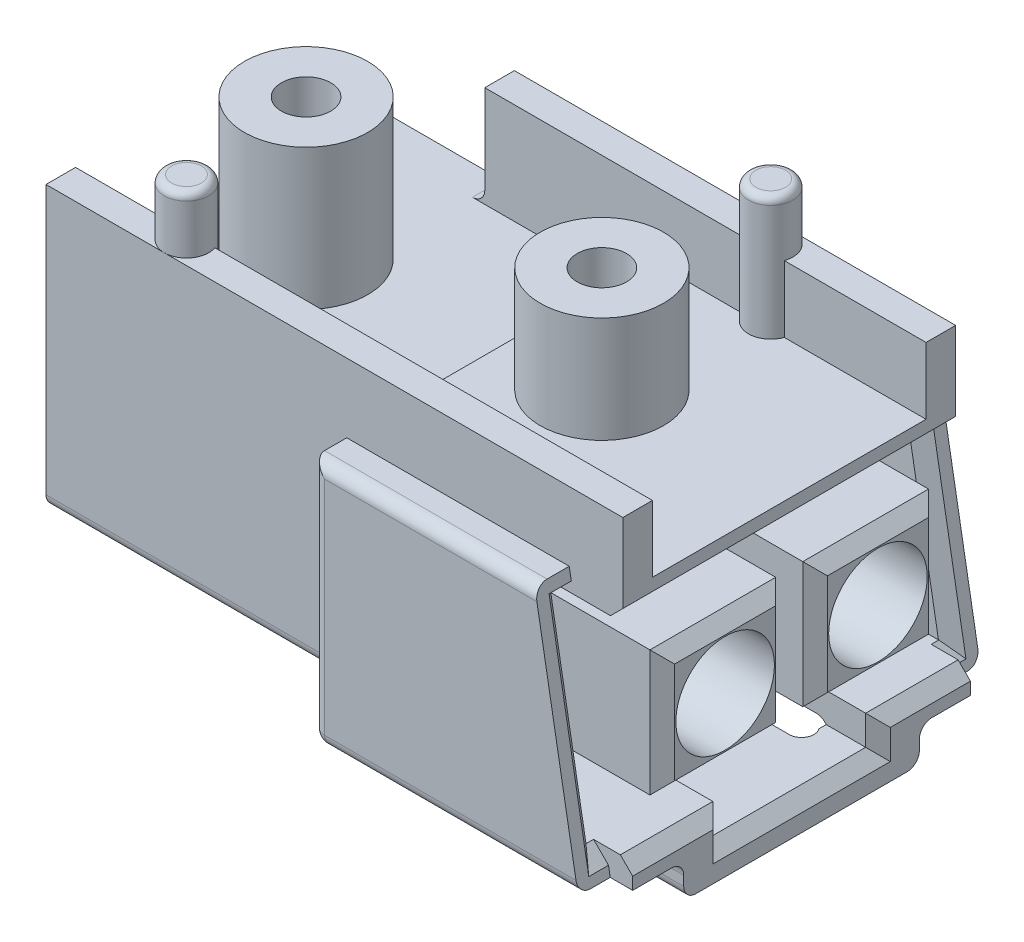
SolidWorks part; units mm, degrees
material "ABS PC"
ref_plane "Front Plane" through (0, 0, 0) normal (0, 0, 1) x (1, 0, 0)
ref_plane "Top Plane" through (0, 0, 0) normal (0, 1, 0) x (1, 0, 0)
ref_plane "Right Plane" through (0, 0, 0) normal (1, 0, 0) x (0, 0, -1)
sketch "Sketch1" plane through (0, 0, 0) normal (0, 0, 1) x (1, 0, 0)
  line L0 (7.1, 7.7) -> (7.1, 0)
  line L1 (-7.1, 7.3) -> (5.1, 7.3)
  line L2 (-7.1, 7.3) -> (-7.1, 0)
  line L3 (7.1, 0) -> (-7.1, 0)
  line L4 (16.3, 7.7) -> (7.1, 7.7)
  line L5 (5.1, 8.7) -> (16.3, 8.7)
  line L6 (16.3, 8.7) -> (16.3, 7.7)
  line L7 (5.1, 8.7) -> (5.1, 7.3)
  dimension "D1" = 14.2
  dimension "D2" = 7.3
  dimension "D3" = 7.7
  dimension "D4" = 1.4
  dimension "D5" = 12.2
  dimension "D6" = 11.2
extrude "Extrude1" add sketch "Sketch1" against normal blind 6.75
chamfer "Chamfer1" distance 0.5 angle 45 1 edges at (16.3, 7.7, -3.375)
sketch "Sketch2" plane through (7.1, 0, 0) normal (1, 0, 0) x (0, 0, -1)
  line L0 (5.65, 6.2) -> (0.55, 6.2)
  line L1 (5.65, 1.1) -> (5.65, 6.2)
  line L2 (0.55, 1.1) -> (5.65, 1.1)
  line L3 (0.55, 6.2) -> (0.55, 1.1)
  line L4 (0, 0) -> (0, 7.7) construction
  line L5 (6.75, 7.7) -> (0, 7.7) construction
  dimension "D1" = 5.1
  dimension "D2" = 5.1
  dimension "D3" = 0.55
  dimension "D4" = 1.5
extrude "Extrude2" add sketch "Sketch2" along normal blind 9.7
chamfer "Chamfer2" distance 0.5 angle 45 4 edges at (16.8, 1.1, -3.1) (16.8, 3.65, -5.65) (16.8, 6.2, -3.1) (16.8, 3.65, -0.55)
ref_plane "Plane1" through (0, 0, -3.1) normal (0, 0, 1) x (1, 0, 0)
sketch "Sketch4" plane through (0, 0, -3.1) normal (0, 0, 1) x (1, 0, 0)
  line L0 (-7.1, 3.65) -> (16.8, 3.65) construction
  line L1 (-7.1, 0.95) -> (2.35, 0.95)
  line L2 (2.35, 0.95) -> (3.4, 2)
  line L3 (5.8, 2.085) -> (6.05, 2.335)
  line L4 (3.4, 2) -> (5.8, 2)
  line L5 (6.05, 2.335) -> (7.95, 2.335)
  line L6 (7.95, 1.65) -> (7.95, 2.335)
  line L7 (7.95, 1.65) -> (16.8, 1.65)
  line L8 (5.8, 2) -> (5.8, 2.085)
  line L9 (16.8, 5.7) -> (16.8, 1.6) construction
  line L10 (-7.1, 0.95) -> (-7.1, 3.65)
  line L11 (16.8, 1.65) -> (16.8, 3.65)
  line L12 (16.8, 3.65) -> (-7.1, 3.65)
  dimension "D1" = 2
  dimension "D3" = 8.85
  dimension "D4" = 0.685
  dimension "D5" = 1.9
  dimension "D6" = 45
  dimension "D7" = 0.3536
  dimension "D8" = 0.085
  dimension "D9" = 2.4
  dimension "D10" = 45
  dimension "D11" = 1.4849
  dimension "D12" = 9.45
revolve "Cut-Revolve1" cut sketch "Sketch4" angle 360 about L0
sketch "Sketch5" plane through (5.1, 0, 0) normal (-1, 0, 0) x (0, 0, 1)
  line L0 (-3.1, -1.401) -> (-8.15, -1.401)
  line L1 (-8.15, 8.6) -> (-8.15, -1.401)
  line L2 (-6.75, 8.6) -> (-8.15, 8.6)
  line L3 (-3.1, 3.65) -> (-3.1, -1.401) construction
  line L4 (-3.1, -1.401) -> (-3.1, 0)
  line L5 (-6.75, 0) -> (0, 0) construction
  line L6 (-3.1, 0) -> (-6.75, 0)
  line L7 (-6.75, 0) -> (-6.75, 7.7) construction
  line L8 (-6.75, 8.6) -> (-6.75, 0)
  circle A0 centre (-3.1, 3.65) radius 1.315 construction
  dimension "D1" = 1.4
  dimension "D2" = 5.051
  dimension "D3" = 5.05
  dimension "D4" = 10.001
extrude "Extrude3" add sketch "Sketch5" against normal up to surface (2 mm away) up to face at (7.1, 3.85, -3.375)
sketch "Sketch6" plane through (0, 8.7, 0) normal (0, 1, 0) x (1, 0, 0)
  line L0 (14.1073, 0) -> (14.1073, 6.75) construction
  line L1 (16.3, 0) -> (5.1, 0) construction
  line L2 (16.3, 6.75) -> (5.1, 6.75) construction
  line L3 (16.3, 6.75) -> (16.3, 0) construction
  dimension "D1" = 2.1927
ref_plane "Plane2" through (15.1697, 2.6748, 0) normal (0.9848, 0.1736, 0) x (0, 0, -1)
sketch "Sketch8" plane through (7.1, 0, 0) normal (1, 0, 0) x (0, 0, -1)
  line L0 (8.15, -1.401) -> (3.1, -1.401) construction
  line L1 (8.15, 8.6) -> (8.15, -1.401) construction
  line L2 (6.75, 8.6) -> (8.15, 8.6) construction
  line L4 (8.15, -1.401) -> (3.1, -1.401)
  line L5 (8.15, 8.6) -> (8.15, -1.401)
  line L6 (6.75, 8.6) -> (8.15, 8.6)
  line L7 (6.75, 8.6) -> (6.75, 7.7)
  line L8 (3.1, -1.401) -> (3.1, -0.4)
  line L10 (3.1, -0.4) -> (7.15, -0.4)
  line L11 (3.1, 0) -> (0, 0) construction
  line L12 (6.75, 7.7) -> (7.15, 7.7)
  line L13 (7.15, 7.7) -> (7.15, -0.4)
  dimension "D1" = 0.4
  dimension "D2" = 0.4
extrude "Extrude5" add sketch "Sketch8" along normal up to surface (7.0249 mm away) up to plane "Plane2"
sketch "Sketch9" plane through (0, 0, -6.75) normal (0, 0, -1) x (-1, 0, 0)
  line L0 (-16.3, 8.7) -> (-16.3, 11.4)
  line L1 (-16.3, 11.4) -> (7.1, 11.4)
  line L2 (7.1, 11.4) -> (7.1, 7.3)
  line L3 (7.1, 7.3) -> (-5.1, 7.3)
  line L4 (-5.1, 7.3) -> (-5.1, 8.7)
  line L5 (-5.1, 8.7) -> (-16.3, 8.7)
  dimension "D1" = 2.7
extrude "Extrude6" add sketch "Sketch9" against normal blind 1.2
sketch "Sketch10" plane through (16.8, 0, 0) normal (1, 0, 0) x (0, 0, -1)
  line L0 (3.1, -0.4) -> (6.85, -0.4)
  line L1 (3.1, -0.4) -> (3.1, -1.6)
  line L2 (0, -1.6) -> (3.1, -1.6)
  line L3 (4.7801, -1.401) -> (6.85, -1.401)
  line L4 (4.7801, -1.401) -> (4.7801, -2.8)
  line L5 (0, -2.8) -> (4.7801, -2.8)
  line L6 (6.85, -0.4) -> (6.85, -1.401)
  line L7 (0, -1.6) -> (0, -2.8)
  line L8 (0, 0) -> (0, 7.7) construction
  line L9 (3.1, -1.401) -> (8.15, -1.401) construction
  point P10 (0, 0)
  dimension "D1" = 3.75
  dimension "D2" = 1.2
  dimension "D3" = 4.7801
  dimension "D4" = 1.2
extrude "Extrude7" add sketch "Sketch10" against normal blind 2
sketch "Sketch11" plane through (0, 0, 0) normal (0, 0, 1) x (1, 0, 0)
  line L0 (16.8, -1.6) -> (16.8, -2.8)
  line L1 (11.25, -1.6) -> (16.8, -1.6)
  line L2 (8.2, -1.6) -> (8.75, -1.6)
  line L3 (8.2, -1.6) -> (8.2, -2.8)
  line L4 (16.8, -2.8) -> (8.2, -2.8)
  arc A0 (11.25, -1.6) -> (8.75, -1.6) centre (10, -2.1766) ccw
  dimension "D3" = 1.3766
  dimension "D1" = 8.6
  dimension "D2" = 1.2
  dimension "D4" = 0.6234
  dimension "D5" = 1.8
  dimension "D6" = 0.55
extrude "Extrude8" add sketch "Sketch11" against normal blind 2
fillet "Fillet1" radius 0.5 12 edges at (10.4942, -1.401, -8.15) (5.1, -1.401, -5.625) (5.1, 3.5995, -8.15) (9.6124, 8.6, -8.15) (14.8, -2.8, -3.3901) (15.8, -2.8, -4.7801) (14.8, -2.1005, -4.7801) (14.8, -2.2, -2) (11.5, -2.8, -2) (8.2, -2.2, -2) (8.2, -2.8, -1) (-1, 0, -6.75)
fillet "Fillet2" radius 0.5 3 edges at (14.8, -1.401, -3.6901) (14.9464, -1.401, -4.6337) (16.05, -1.401, -4.7801)
chamfer "Chamfer4" distance 0.5 angle 45 6 edges at (15.7118, -0.4, -7) (14.2836, 7.7, -6.95) (14.9977, 3.65, -7.15) (16.8, -1.6, -1.55) (16.8, -1, -3.1) (16.8, -0.4, -4.975) first distance on face at (13.2039, -0.4, -5.7) first distance on face at (12.3945, 7.7, -4.6333) first distance on face at (11.0489, 3.65, -7.15) first distance on face at (14.2923, -1.6, -1.8396) first distance on face at (10.2799, -0.8622, -3.1)
sketch "Sketch13" plane through (0, 7.3, 0) normal (0, 1, 0) x (1, 0, 0)
  line L1 (5.1, 0) -> (-7.1, 0) construction
  line L2 (-7.1, 5.55) -> (-7.1, 0) construction
  line L3 (-0.8, 0) -> (-2.3, 0)
  line L4 (-4.3, 0) -> (-5.8, 0)
  arc A0 (-0.8, 0) -> (-5.8, 0) centre (-3.3, 0) ccw
  arc A1 (-2.3, 0) -> (-4.3, 0) centre (-3.3, 0) ccw
  dimension "D1" = 5
  dimension "D3" = 2
  dimension "D2" = 3.8
extrude "Extrude9" add sketch "Sketch13" along normal blind 5.7
sketch "Sketch14" plane through (0, 8.7, 0) normal (0, 1, 0) x (1, 0, 0)
  line L0 (16.3, 0) -> (5.1, 0) construction
  line L1 (5.1, 5.55) -> (5.1, 0) construction
  line L2 (11.2, 0) -> (9.7, 0)
  line L3 (7.7, 0) -> (6.2, 0)
  arc A0 (11.2, 0) -> (6.2, 0) centre (8.7, 0) ccw
  arc A1 (9.7, 0) -> (7.7, 0) centre (8.7, 0) ccw
  dimension "D2" = 5
  dimension "D3" = 2
  dimension "D1" = 3.6
extrude "Extrude10" add sketch "Sketch14" along normal blind 4.3
mirror "Mirror1" about plane through (0, 0, 0) normal (0, 0, 1) of bodies 111
sketch "Sketch15" plane through (0, 0, -6.75) normal (0, 0, -1) x (-1, 0, 0)
  line L0 (-5.1, 7.3) -> (7.1, 7.3) construction
  line L1 (-5.1, 7.3) -> (7.1, 7.3) construction
  line L2 (7.1, 7.3) -> (1.6, 7.3)
  line L3 (1.6, 7.3) -> (1.6, 11.4)
  line L5 (7.1, 11.4) -> (-16.3, 11.4) construction
  line L6 (1.6, 11.4) -> (7.1, 11.4)
  line L7 (7.1, 11.4) -> (7.1, 7.3)
  dimension "D1" = 5.5
extrude "Cut-Extrude1" cut sketch "Sketch15" against normal up to surface (1.2 mm away) up to face at (4.7667, 9.1333, -5.55)
fillet "Fillet3" radius 0.5 1 edges at (-1.6, 7.3, -6.15)
sketch "Sketch16" plane through (0, 7.3, 0) normal (0, 1, 0) x (1, 0, 0)
  line L0 (-7.1, -6.75) -> (16.3, -6.75) construction
  line L1 (-7.1, 6.75) -> (-7.1, -5.55) construction
  circle A0 centre (-2.3, -5.85) radius 0.9
  dimension "D1" = 1.8
  dimension "D2" = 0.9
  dimension "D3" = 4.8
extrude "Extrude11" add sketch "Sketch16" along normal blind 6.4
sketch "Sketch17" plane through (0, 8.7, 0) normal (0, 1, 0) x (1, 0, 0)
  line L0 (-1.6, 6.75) -> (16.3, 6.75) construction
  line L1 (16.3, 5.55) -> (16.3, 6.75) construction
  circle A0 centre (9.7, 5.85) radius 0.9
  dimension "D1" = 1.8
  dimension "D2" = 0.9
  dimension "D3" = 6.6
extrude "Extrude12" add sketch "Sketch17" along normal blind 5
fillet "Fillet4" radius 0.3 2 edges at (8.8, 13.7, -5.85) (-3.2, 13.7, 5.85)
